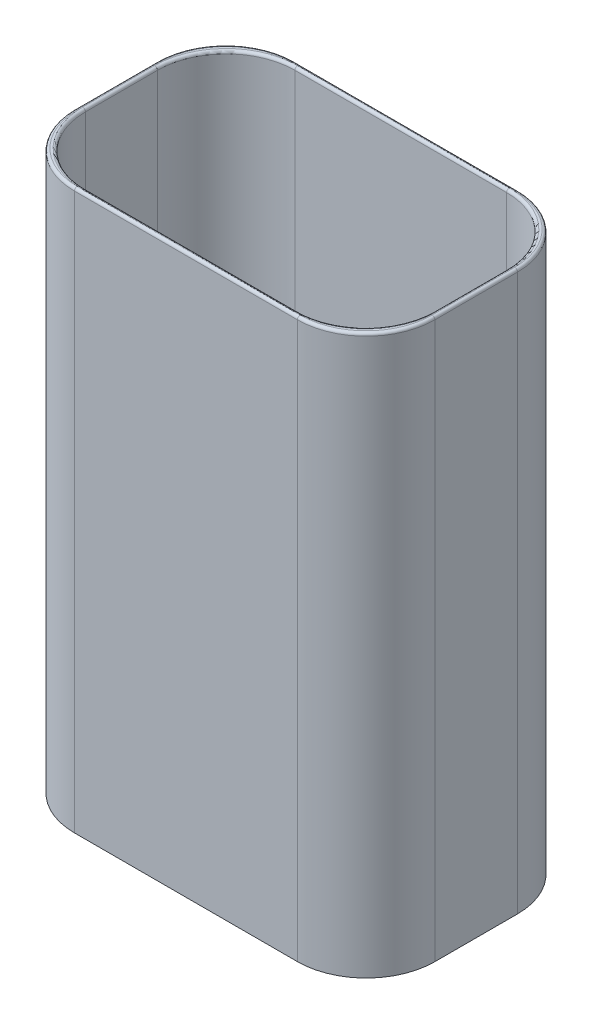
SolidWorks part; units mm, degrees
ref_plane "Front Plane" through (0, 0, 0) normal (0, 0, 1) x (1, 0, 0)
ref_plane "Top Plane" through (0, 0, 0) normal (0, 1, 0) x (1, 0, 0)
ref_plane "Right Plane" through (0, 0, 0) normal (1, 0, 0) x (0, 0, -1)
sketch "Sketch1" plane through (0, 0, 0) normal (0, 1, 0) x (1, 0, 0)
  line L0 (-30.7328, 41.9711) -> (-32.7963, 43.9056)
  line L1 (-30.7328, 41.9711) -> (96.2672, 41.9711)
  line L2 (-30.7328, 41.9711) -> (-30.7328, -34.2289)
  line L3 (-30.7328, -34.2289) -> (96.2672, -34.2289)
  line L4 (96.2672, 41.9711) -> (96.2672, -34.2289)
  line L5 (-32.7963, 43.9056) -> (98.3306, 43.9056)
  line L6 (-32.7963, 43.9056) -> (-32.7963, -36.1634)
  line L7 (-32.7963, -36.1634) -> (98.3306, -36.1634)
  line L8 (98.3306, 43.9056) -> (98.3306, -36.1634)
  line L9 (96.2672, 41.9711) -> (98.3306, 43.9056)
  line L10 (96.2672, -34.2289) -> (98.3306, -36.1634)
  dimension "D1" = 76.2
  dimension "D2" = 127
  dimension "D3" = 2.8284
extrude "Boss-Extrude1" add sketch "Sketch1" along normal blind 2 contours L4 L1 L2 L3 | L10 L3 L2 L0 L6 L7 | L4 L10 L8 L9 | L1 L9 L5 L0 region at (-32.2692, 0, -3.8711) region at (32.7672, 0, -42.9435) region at (32.7672, 0, -3.8711) region at (97.3074, 0, -3.8711)
extrude "Boss-Extrude2" add sketch "Sketch1<3>" along normal blind 203.2 contours L4 L10 L8 L9 | L1 L9 L5 L0 | L10 L3 L2 L0 L6 L7 region at (-32.2692, 0, -3.8711) region at (32.7672, 0, -42.9435) region at (97.3074, 0, -3.8711)
sketch "Sketch1<3>" plane through (0, 0, 0) normal (0, 1, 0) x (1, 0, 0) same geometry as "Sketch1"
fillet "Fillet2" radius 25 8 edges at (-32.7963, 101.6, -43.9056) (-32.7963, 101.6, 36.1634) (98.3306, 101.6, 36.1634) (98.3306, 101.6, -43.9056) (-30.7328, 102.6, -41.9711) (-30.7328, 102.6, 34.2289) (96.2672, 102.6, 34.2289) (96.2672, 102.6, -41.9711)
fillet "Fillet3" radius 15 8 edges at (88.9448, 2, -34.6488) (96.2672, 2, -3.8711) (88.9448, 2, 26.9065) (32.7672, 2, 34.2289) (-23.4105, 2, 26.9065) (-30.7328, 2, -3.8711) (-23.4105, 2, -34.6488) (32.7672, 2, -41.9711)
fillet "Fillet4" radius 1 16 edges at (-25.4739, 203.2, 28.841) (-32.7963, 203.2, -3.8711) (-25.4739, 203.2, -36.5833) (32.7672, 203.2, -43.9056) (91.0083, 203.2, -36.5833) (98.3306, 203.2, -3.8711) (91.0083, 203.2, 28.841) (-23.4105, 203.2, 26.9065) (-30.7328, 203.2, -3.8711) (-23.4105, 203.2, -34.6488) (32.7672, 203.2, -41.9711) (88.9448, 203.2, -34.6488) (96.2672, 203.2, -3.8711) (88.9448, 203.2, 26.9065) (32.7672, 203.2, 36.1634) (32.7672, 203.2, 34.2289)
